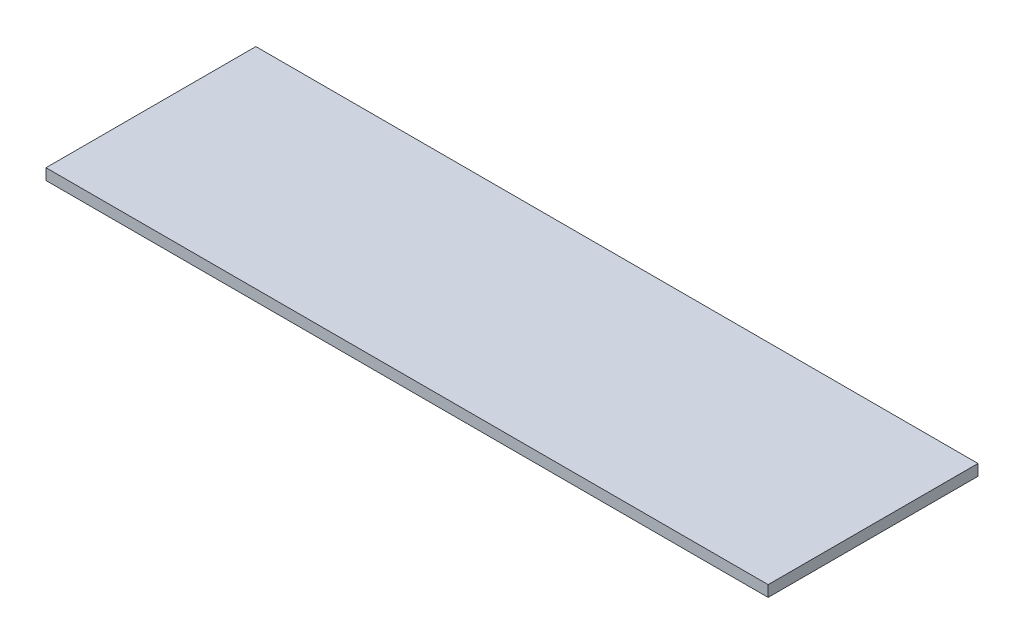
SolidWorks part; units mm, degrees
ref_plane "Alzado" through (0, 0, 0) normal (0, 0, 1) x (1, 0, 0)
ref_plane "Planta" through (0, 0, 0) normal (0, 1, 0) x (1, 0, 0)
ref_plane "Vista lateral" through (0, 0, 0) normal (1, 0, 0) x (0, 0, -1)
sketch "Croquis1" plane through (0, 0, 0) normal (0, 1, 0) x (1, 0, 0)
  line L1 (-585, 170) -> (585, 170)
  line L2 (-585, 170) -> (-585, -170)
  line L3 (-585, -170) -> (585, -170)
  line L4 (585, 170) -> (585, -170)
  line L5 (-585, 170) -> (585, -170) construction
  line L6 (-585, -170) -> (585, 170) construction
  point P0 (0, 0)
  dimension "D1" = 1170
  dimension "D2" = 340
extrude "Saliente-Extruir1" add sketch "Croquis1" along normal blind 18
